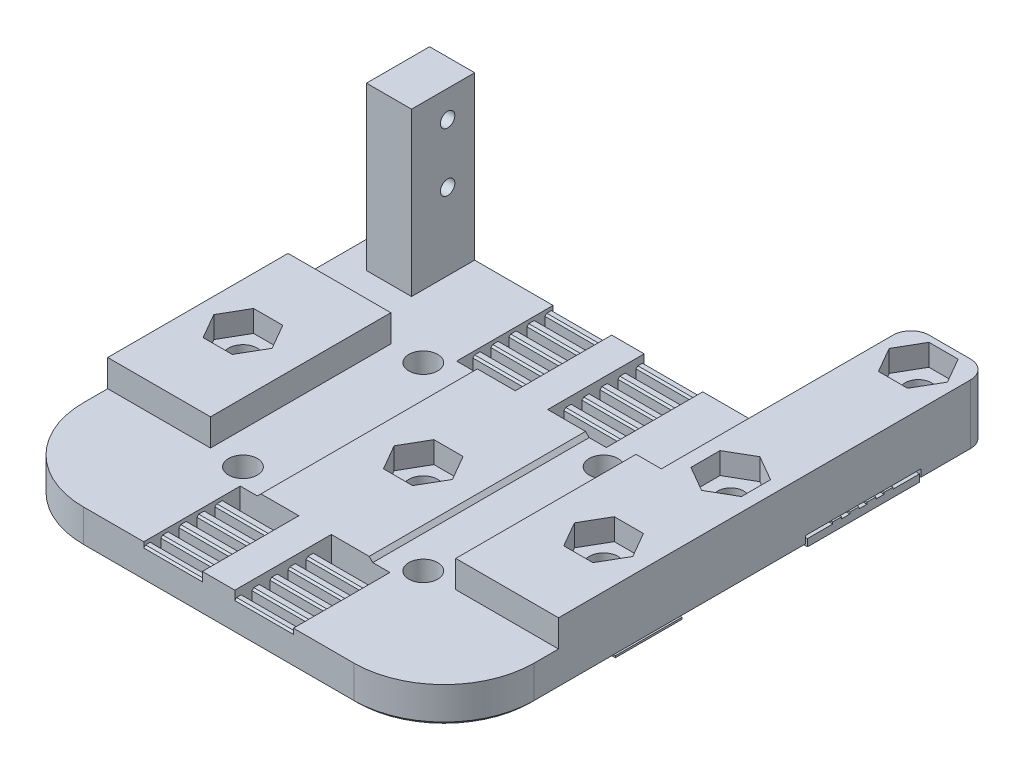
SolidWorks part; units mm, degrees
ref_plane "前视基准面" through (0, 0, 0) normal (0, 0, 1) x (1, 0, 0)
ref_plane "上视基准面" through (0, 0, 0) normal (0, 1, 0) x (1, 0, 0)
ref_plane "右视基准面" through (0, 0, 0) normal (1, 0, 0) x (0, 0, -1)
other "Configuration Table"
sketch "草图1" plane through (0, 0, 0) normal (0, 1, 0) x (1, 0, 0)
  line L1 (0, 0) -> (50, 0)
  line L2 (0, 0) -> (0, 45.4)
  line L3 (0, 45.4) -> (50, 45.4)
  line L4 (50, 0) -> (50, 45.4)
  circle A0 centre (15, 32.7) radius 1.6
  circle A1 centre (35, 32.7) radius 1.6
  circle A2 centre (35, 12.7) radius 1.6
  circle A3 centre (15, 12.7) radius 1.6
  dimension "D3" = 3.2
  dimension "D1" = 50
  dimension "D2" = 45.4
  dimension "D6" = 12.7
  dimension "D7" = 15
  dimension "D5" = 2
extrude "凸台-拉伸1" add sketch "草图1" along normal blind 4
sketch "草图2" plane through (0, 0, 0) normal (0, 0, 1) x (1, 0, 0)
  line L0 (0, 4) -> (50, 4) construction
  line L1 (19, 4) -> (31, 4)
  line L2 (19, 4) -> (19, 4.4)
  line L3 (19, 4.4) -> (31, 4.4)
  line L4 (31, 4) -> (31, 4.4)
  line L5 (0, 0) -> (50, 0) construction
  point P6 (25, 4.4)
  point P9 (25, 0)
  dimension "D1" = 0.4
  dimension "D2" = 12
  dimension "D3" = 0
extrude "凸台-拉伸2" add sketch "草图2" against normal up to surface (45.4 mm away) up to face at (25, 2, -45.4)
chamfer "倒角1" distance 0.4 angle 45 2 edges at (31, 4, -22.7) (19, 4, -22.7)
sketch "草图3" plane through (0, 0, 0) normal (0, -1, 0) x (-1, 0, 0)
  line L0 (0, 45.4) -> (0, 0) construction
  line L1 (0, 18.2) -> (-50, 18.2)
  line L2 (0, 18.2) -> (0, 27.2)
  line L3 (0, 27.2) -> (-50, 27.2)
  line L4 (-50, 18.2) -> (-50, 27.2)
  line L5 (-50, 0) -> (-50, 45.4) construction
  line L6 (0, 0) -> (-50, 0) construction
  point P8 (0, 22.7)
  dimension "D1" = 9
  dimension "D2" = 22.7
extrude "切除-拉伸1" cut sketch "草图3" against normal blind 0.4
sketch "草图4" plane through (0, 0.4, 0) normal (0, -1, 0) x (-1, 0, 0)
  line L0 (0, 18.2) -> (0, 27.2) construction
  circle A0 centre (-5, 22.7) radius 1.6
  circle A1 centre (-25, 22.7) radius 1.6
  circle A2 centre (-45, 22.7) radius 1.6
  point P4 (0, 22.7)
  dimension "D1" = 3.2
  dimension "D4" = 5
extrude "切除-拉伸2" cut sketch "草图4" against normal through all
sketch "草图5" plane through (0, 4, 0) normal (0, 1, 0) x (1, 0, 0)
  line L0 (50, 45.4) -> (31.4, 45.4) construction
  line L1 (50, 45.4) -> (41.4, 45.4)
  line L2 (50, 45.4) -> (50, 60.4)
  line L3 (50, 60.4) -> (41.4, 60.4)
  line L4 (41.4, 45.4) -> (41.4, 60.4)
  line L5 (50, 0) -> (50, 45.4) construction
  dimension "D1" = 8.6
  dimension "D2" = 0
  dimension "D3" = 15
extrude "凸台-拉伸3" add sketch "草图5" against normal blind 4
sketch "草图6" plane through (0, 0, 0) normal (0, -1, 0) x (1, 0, 0)
  line L0 (50, -60.4) -> (41.4, -60.4) construction
  line L1 (50, -27.2) -> (50, -60.4) construction
  circle A0 centre (45.7, -56.9) radius 1.45
  circle A1 centre (45.7, -36.1) radius 1.45
  point P4 (45.7, -60.4)
  dimension "D1" = 2.9
  dimension "D2" = 3.5
  dimension "D3" = 4.3
  dimension "D4" = 0
  dimension "D5" = 20.8
  dimension "D6" = 2.9
extrude "切除-拉伸3" cut sketch "草图6" against normal blind 4
sketch "草图7" plane through (0, 4.4, 0) normal (0, 1, 0) x (1, 0, 0)
  line L1 (28.2332, 22.7) -> (26.6166, 25.5)
  line L2 (26.6166, 25.5) -> (23.3834, 25.5)
  line L3 (23.3834, 25.5) -> (21.7668, 22.7)
  line L4 (21.7668, 22.7) -> (23.3834, 19.9)
  line L5 (23.3834, 19.9) -> (26.6166, 19.9)
  line L6 (26.6166, 19.9) -> (28.2332, 22.7)
  circle A0 centre (25, 22.7) radius 2.8 construction
  dimension "D1" = 5.6
extrude "切除-拉伸4" cut sketch "草图7" against normal blind 2.4
sketch "草图8" plane through (0, 4, 0) normal (0, 1, 0) x (1, 0, 0)
  line L0 (50, 0) -> (50, 60.4) construction
  line L1 (41.4, 32.7) -> (38.6, 32.7)
  line L2 (50, 32.7) -> (50, 12.7)
  line L3 (50, 12.7) -> (38.6, 12.7)
  line L4 (38.6, 32.7) -> (38.6, 12.7)
  line L5 (0, 45.4) -> (0, 0) construction
  line L6 (0, 32.7) -> (11.4, 32.7)
  line L7 (0, 32.7) -> (0, 12.7)
  line L8 (0, 12.7) -> (11.4, 12.7)
  line L9 (11.4, 32.7) -> (11.4, 12.7)
  line L11 (41.4, 60.4) -> (50, 60.4)
  line L12 (41.4, 60.4) -> (41.4, 32.7)
  line L14 (50, 60.4) -> (50, 32.7)
  circle A1 centre (5, 22.7) radius 1.6 construction
  circle A2 centre (45, 22.7) radius 1.6 construction
  circle A3 centre (5, 22.7) radius 1.6
  circle A4 centre (45, 22.7) radius 1.6
  circle A5 centre (45.7, 56.9) radius 1.45
  circle A6 centre (45.7, 36.1) radius 1.45
  point P12 (50, 22.7)
  point P14 (11.4, 22.7)
  dimension "D1" = 27.2
  dimension "D2" = 11.4
  dimension "D3" = 20
  dimension "D4" = 20
extrude "凸台-拉伸4" add sketch "草图8" along normal blind 3
sketch "草图9" plane through (0, 7, 0) normal (0, 1, 0) x (1, 0, 0)
  line L0 (50, 12.7) -> (50, 60.4) construction
  line L1 (8.2332, 22.7) -> (6.6166, 25.5)
  line L2 (6.6166, 25.5) -> (3.3834, 25.5)
  line L3 (3.3834, 25.5) -> (1.7668, 22.7)
  line L4 (1.7668, 22.7) -> (3.3834, 19.9)
  line L5 (3.3834, 19.9) -> (6.6166, 19.9)
  line L6 (6.6166, 19.9) -> (8.2332, 22.7)
  line L7 (48.2332, 22.7) -> (46.6166, 25.5)
  line L8 (46.6166, 25.5) -> (43.3834, 25.5)
  line L9 (43.3834, 25.5) -> (41.7668, 22.7)
  line L10 (41.7668, 22.7) -> (43.3834, 19.9)
  line L11 (43.3834, 19.9) -> (46.6166, 19.9)
  line L12 (46.6166, 19.9) -> (48.2332, 22.7)
  line L13 (44.0834, 54.1) -> (47.3166, 54.1)
  line L14 (47.3166, 54.1) -> (48.9332, 56.9)
  line L15 (48.9332, 56.9) -> (47.3166, 59.7)
  line L16 (47.3166, 59.7) -> (44.0834, 59.7)
  line L17 (44.0834, 59.7) -> (42.4668, 56.9)
  line L18 (42.4668, 56.9) -> (44.0834, 54.1)
  line L19 (48.5, 37.7166) -> (45.7, 39.3332)
  line L20 (45.7, 39.3332) -> (42.9, 37.7166)
  line L21 (42.9, 37.7166) -> (42.9, 34.4834)
  line L22 (42.9, 34.4834) -> (45.7, 32.8668)
  line L23 (45.7, 32.8668) -> (48.5, 34.4834)
  line L24 (48.5, 34.4834) -> (48.5, 37.7166)
  circle A0 centre (5, 22.7) radius 2.8 construction
  circle A1 centre (45, 22.7) radius 2.8 construction
  circle A2 centre (45.7, 56.9) radius 2.8 construction
  circle A3 centre (45.7, 36.1) radius 2.8 construction
  dimension "D1" = 5.6
  dimension "D2" = 5.6
  dimension "D3" = 5.6
  dimension "D4" = 5.6
  dimension "D5" = 0
  dimension "D6" = 90
extrude "切除-拉伸5" cut sketch "草图9" against normal blind 2.4
sketch "草图10" plane through (0, 4, 0) normal (0, 1, 0) x (1, 0, 0)
  line L1 (3, 38.4) -> (8, 38.4)
  line L2 (3, 38.4) -> (3, 45.4)
  line L3 (3, 45.4) -> (8, 45.4)
  line L4 (8, 38.4) -> (8, 45.4)
  line L7 (18.6, 45.4) -> (0, 45.4) construction
  line L8 (0, 45.4) -> (0, 32.7) construction
  dimension "D1" = 7
  dimension "D2" = 5
  dimension "D3" = 3
  dimension "D4" = 0
extrude "凸台-拉伸5" add sketch "草图10" along normal blind 18
sketch "草图11" plane through (3, 0, 0) normal (-1, 0, 0) x (0, 0, 1)
  line L0 (-45.4, 22) -> (-45.4, 4) construction
  line L1 (-45.4, 22) -> (-38.4, 22) construction
  circle A0 centre (-42.4, 19) radius 0.8
  circle A1 centre (-42.4, 12.5) radius 0.8
  dimension "D1" = 6.5
  dimension "D2" = 0
  dimension "D3" = 1.6
  dimension "D4" = 1.6
  dimension "D5" = 3
  dimension "D6" = 3
extrude "切除-拉伸6" cut sketch "草图11" against normal blind 15
sketch "草图12" plane through (0, 4.4, 0) normal (0, 1, 0) x (1, 0, 0)
  line L0 (19, 45.4) -> (31, 45.4) construction
  line L1 (26.8, 45.4) -> (33.3, 45.4)
  line L2 (26.8, 45.4) -> (26.8, 34.7)
  line L3 (26.8, 34.7) -> (33.3, 34.7)
  line L4 (33.3, 45.4) -> (33.3, 34.7)
  line L5 (18.6, 45.4) -> (8, 45.4) construction
  line L6 (16.7, 45.4) -> (23.2, 45.4)
  line L7 (16.7, 45.4) -> (16.7, 34.7)
  line L8 (16.7, 34.7) -> (23.2, 34.7)
  line L9 (23.2, 45.4) -> (23.2, 34.7)
  line L10 (0, 0) -> (18.6, 0) construction
  line L11 (16.7, 0) -> (23.2, 0)
  line L12 (16.7, 0) -> (16.7, 10.7)
  line L13 (16.7, 10.7) -> (23.2, 10.7)
  line L14 (23.2, 0) -> (23.2, 10.7)
  line L16 (26.8, 10.7) -> (33.3, 10.7)
  line L17 (26.8, 10.7) -> (26.8, 0)
  line L18 (26.8, 0) -> (33.3, 0)
  line L19 (33.3, 10.7) -> (33.3, 0)
  circle A0 centre (25, 22.7) radius 1.6 construction
  dimension "D12" = 12
  dimension "D1" = 6.5
  dimension "D2" = 3.6
  dimension "D3" = 6.5
  dimension "D4" = 6.5
  dimension "D5" = 6.5
  dimension "D6" = 3.6
  dimension "D7" = 1.8
  dimension "D8" = 1.8
  dimension "D9" = 12
  dimension "D10" = 12
  dimension "D11" = 12
extrude "切除-拉伸7" cut sketch "草图12" against normal blind 0.8
sketch "草图13" plane through (0, 3.6, 0) normal (0, 1, 0) x (1, 0, 0)
  line L0 (23.2, 34.7) -> (23.2, 45.4) construction
  line L1 (16.7, 34.7) -> (23.2, 34.7)
  line L2 (16.7, 34.7) -> (16.7, 36.5)
  line L3 (16.7, 36.5) -> (23.2, 36.5)
  line L4 (23.2, 34.7) -> (23.2, 36.5)
  line L5 (33.3, 34.7) -> (33.3, 45.4) construction
  line L6 (26.8, 34.7) -> (33.3, 34.7)
  line L7 (26.8, 34.7) -> (26.8, 36.5)
  line L8 (26.8, 36.5) -> (33.3, 36.5)
  line L9 (33.3, 34.7) -> (33.3, 36.5)
  line L10 (23.2, 0) -> (23.2, 10.7) construction
  line L11 (16.7, 10.7) -> (23.2, 10.7)
  line L12 (16.7, 10.7) -> (16.7, 8.9)
  line L13 (16.7, 8.9) -> (23.2, 8.9)
  line L14 (23.2, 10.7) -> (23.2, 8.9)
  line L15 (33.3, 0) -> (33.3, 10.7) construction
  line L16 (26.8, 10.7) -> (33.3, 10.7)
  line L17 (26.8, 10.7) -> (26.8, 8.9)
  line L18 (26.8, 8.9) -> (33.3, 8.9)
  line L19 (33.3, 10.7) -> (33.3, 8.9)
  dimension "D1" = 1.8
  dimension "D2" = 1.8
  dimension "D3" = 1.8
  dimension "D4" = 1.8
extrude "切除-拉伸8" cut sketch "草图13" against normal through all
sketch "草图14" plane through (0, 3.6, 0) normal (0, 1, 0) x (1, 0, 0)
  line L0 (16.7, 34.7) -> (16.7, 45.4) construction
  line L1 (16.7, 37.5) -> (23.2, 37.5)
  line L2 (16.7, 37.5) -> (16.7, 38.5)
  line L3 (16.7, 38.5) -> (23.2, 38.5)
  line L4 (23.2, 37.5) -> (23.2, 38.5)
  line L5 (23.2, 36.5) -> (23.2, 45.4) construction
  line L6 (23.2, 36.5) -> (16.7, 36.5) construction
  line L7 (16.7, 39.5) -> (16.7, 40.5)
  line L8 (16.7, 39.5) -> (23.2, 39.5)
  line L9 (23.2, 39.5) -> (23.2, 40.5)
  line L10 (16.7, 40.5) -> (23.2, 40.5)
  line L11 (16.7, 41.5) -> (16.7, 42.5)
  line L12 (16.7, 41.5) -> (23.2, 41.5)
  line L13 (23.2, 41.5) -> (23.2, 42.5)
  line L14 (16.7, 42.5) -> (23.2, 42.5)
  line L15 (16.7, 43.5) -> (16.7, 44.5)
  line L16 (16.7, 43.5) -> (23.2, 43.5)
  line L17 (23.2, 43.5) -> (23.2, 44.5)
  line L18 (16.7, 44.5) -> (23.2, 44.5)
  line L19 (33.3, 36.5) -> (33.3, 45.4) construction
  line L20 (33.3, 37.5) -> (26.8, 37.5)
  line L21 (33.3, 37.5) -> (33.3, 38.5)
  line L22 (33.3, 38.5) -> (26.8, 38.5)
  line L23 (26.8, 37.5) -> (26.8, 38.5)
  line L24 (26.8, 45.4) -> (26.8, 36.5) construction
  line L25 (33.3, 39.5) -> (33.3, 40.5)
  line L26 (33.3, 39.5) -> (26.8, 39.5)
  line L27 (26.8, 39.5) -> (26.8, 40.5)
  line L28 (33.3, 40.5) -> (26.8, 40.5)
  line L29 (33.3, 41.5) -> (33.3, 42.5)
  line L30 (33.3, 41.5) -> (26.8, 41.5)
  line L31 (26.8, 41.5) -> (26.8, 42.5)
  line L32 (33.3, 42.5) -> (26.8, 42.5)
  line L33 (33.3, 43.5) -> (33.3, 44.5)
  line L34 (33.3, 43.5) -> (26.8, 43.5)
  line L35 (26.8, 43.5) -> (26.8, 44.5)
  line L36 (33.3, 44.5) -> (26.8, 44.5)
  line L37 (33.3, 10.7) -> (33.3, 0) construction
  line L38 (33.3, 7.9) -> (26.8, 7.9)
  line L39 (33.3, 7.9) -> (33.3, 6.9)
  line L40 (33.3, 6.9) -> (26.8, 6.9)
  line L41 (26.8, 7.9) -> (26.8, 6.9)
  line L42 (23.2, 0) -> (23.2, 8.9) construction
  line L43 (23.2, 7.9) -> (16.7, 7.9)
  line L44 (23.2, 7.9) -> (23.2, 6.9)
  line L45 (23.2, 6.9) -> (16.7, 6.9)
  line L46 (16.7, 7.9) -> (16.7, 6.9)
  line L47 (16.7, 8.9) -> (16.7, 0) construction
  line L48 (26.8, 8.9) -> (33.3, 8.9) construction
  line L49 (16.7, 8.9) -> (23.2, 8.9) construction
  line L50 (33.3, 5.9) -> (33.3, 4.9)
  line L51 (33.3, 5.9) -> (26.8, 5.9)
  line L52 (26.8, 5.9) -> (26.8, 4.9)
  line L53 (33.3, 4.9) -> (26.8, 4.9)
  line L54 (23.2, 5.9) -> (23.2, 4.9)
  line L55 (23.2, 5.9) -> (16.7, 5.9)
  line L56 (16.7, 5.9) -> (16.7, 4.9)
  line L57 (23.2, 4.9) -> (16.7, 4.9)
  line L58 (33.3, 3.9) -> (33.3, 2.9)
  line L59 (33.3, 3.9) -> (26.8, 3.9)
  line L60 (26.8, 3.9) -> (26.8, 2.9)
  line L61 (33.3, 2.9) -> (26.8, 2.9)
  line L62 (23.2, 3.9) -> (23.2, 2.9)
  line L63 (23.2, 3.9) -> (16.7, 3.9)
  line L64 (16.7, 3.9) -> (16.7, 2.9)
  line L65 (23.2, 2.9) -> (16.7, 2.9)
  line L66 (33.3, 1.9) -> (33.3, 0.9)
  line L67 (33.3, 1.9) -> (26.8, 1.9)
  line L68 (26.8, 1.9) -> (26.8, 0.9)
  line L69 (33.3, 0.9) -> (26.8, 0.9)
  line L70 (23.2, 1.9) -> (23.2, 0.9)
  line L71 (23.2, 1.9) -> (16.7, 1.9)
  line L72 (16.7, 1.9) -> (16.7, 0.9)
  line L73 (23.2, 0.9) -> (16.7, 0.9)
  dimension "D1" = 1
  dimension "D2" = 1
  dimension "D5" = 1
  dimension "D6" = 1
  dimension "D7" = 1
  dimension "D8" = 1
  dimension "D3" = 4
  dimension "D4" = 4
  dimension "D9" = 4
extrude "切除-拉伸9" cut sketch "草图14" against normal blind 1.2
fillet "圆角1" radius 10 2 edges at (50, 2, 0) (0, 2, 0)
fillet "圆角2" radius 2 3 edges at (41.4, 3.5, -60.4) (50, 3.5, -60.4) (0, 2, -45.4)
sketch "草图15" plane through (0, 0, 0) normal (0, -1, 0) x (1, 0, 0)
  line L0 (50, -18.2) -> (0, -18.2) construction
  line L1 (0, -19) -> (50, -19)
  line L2 (0, -19) -> (0, -26.4)
  line L3 (0, -26.4) -> (50, -26.4)
  line L4 (50, -19) -> (50, -26.4)
  line L5 (0, -27.2) -> (50, -27.2) construction
  line L6 (0, -18.2) -> (0, -27.2) construction
  line L7 (50, -27.2) -> (50, -18.2) construction
  dimension "D1" = 0.8
  dimension "D2" = 0.8
  dimension "D3" = 0
  dimension "D4" = 0
extrude "凸台-拉伸6" add sketch "草图15" against normal blind 0.2 separate body
sketch "草图16" plane through (0, 0, 0) normal (0, -1, 0) x (-1, 0, 0)
  line L14 (-48.421, 52.9) -> (-42.4, 52.9)
  line L16 (-48.5, 49.901) -> (-42.4, 49.901)
  line L17 (-42.4, 52.9) -> (-42.4, 49.901)
  line L18 (-48.5, 43.099) -> (-42.4, 43.099)
  line L20 (-48.421, 40.1) -> (-42.4, 40.1)
  line L21 (-42.4, 43.099) -> (-42.4, 40.1)
  line L22 (-41.4, 58.4) -> (-41.4, 45.4) construction
  line L24 (-48.421, 52.9) -> (-50, 52.9)
  line L25 (-48.5, 49.901) -> (-48.5, 43.099)
  line L26 (-48.421, 40.1) -> (-50, 40.1)
  line L27 (-50, 52.9) -> (-50, 40.1)
  circle A2 centre (-45.7, 36.1) radius 1.45 construction
  circle A3 centre (-45.7, 56.9) radius 1.45 construction
  dimension "D6" = 4
  dimension "D1" = 1.5
  dimension "D3" = 1
  dimension "D4" = 1
  dimension "D5" = 4
  dimension "D7" = 3
  dimension "D8" = 3
extrude "切除-拉伸10" cut sketch "草图16" against normal blind 1.2
chamfer "倒角2" distance 0.2 angle 45 40 edges at (30.05, 3.6, -7.9) (30.05, 3.6, -8.9) (30.05, 3.6, -5.9) (30.05, 3.6, -6.9) (30.05, 3.6, -3.9) (30.05, 3.6, -4.9) (30.05, 3.6, -1.9) (30.05, 3.6, -2.9) (30.05, 3.6, 0) (30.05, 3.6, -0.9) (19.95, 3.6, 0) (19.95, 3.6, -0.9) (19.95, 3.6, -1.9) (19.95, 3.6, -2.9) (19.95, 3.6, -3.9) (19.95, 3.6, -4.9) (19.95, 3.6, -5.9) (19.95, 3.6, -6.9) (19.95, 3.6, -7.9) (19.95, 3.6, -8.9) (30.05, 3.6, -41.5) (30.05, 3.6, -45.4) (30.05, 3.6, -44.5) (30.05, 3.6, -43.5) (30.05, 3.6, -42.5) (30.05, 3.6, -40.5) (30.05, 3.6, -39.5) (30.05, 3.6, -38.5) (30.05, 3.6, -37.5) (30.05, 3.6, -36.5) (19.95, 3.6, -36.5) (19.95, 3.6, -37.5) (19.95, 3.6, -38.5) (19.95, 3.6, -39.5) (19.95, 3.6, -40.5) (19.95, 3.6, -41.5) (19.95, 3.6, -42.5) (19.95, 3.6, -43.5) (19.95, 3.6, -44.5) (19.95, 3.6, -45.4)
chamfer "倒角3" distance 0.4 angle 45 45 edges at (35, 0, -31.1) (15, 0, -31.1) (25, 0, -27.2) (50, 0, -55.65) (50, 0, -33.65) (49.4142, 0, -59.8142) (45.7, 0, -60.4) (41.9858, 0, -59.8142) (41.4, 0, -51.9) (21.7, 0, -45.4) (0.5858, 0, -44.8142) (0, 0, -35.3) (45.7, 0, -37.55) (45.7, 0, -58.35) (19.95, 0, -36.5) (23.2, 0, -35.6) (19.95, 0, -34.7) (16.7, 0, -35.6) (30.05, 0, -36.5) (33.3, 0, -35.6) (30.05, 0, -34.7) (26.8, 0, -35.6) (35, 0, -11.1) (15, 0, -11.1) (25, 0, -18.2) (0, 0, -14.1) (2.9289, 0, -2.9289) (25, 0, 0) (47.0711, 0, -2.9289) (50, 0, -14.1) (30.05, 0, -10.7) (33.3, 0, -9.8) (30.05, 0, -8.9) (26.8, 0, -9.8) (19.95, 0, -10.7) (23.2, 0, -9.8) (19.95, 0, -8.9) (16.7, 0, -9.8) (46.2, 0, -40.1) (42.4, 0, -41.5995) (45.45, 0, -43.099) (48.5, 0, -46.5) (45.45, 0, -49.901) (42.4, 0, -51.4005) (46.2, 0, -52.9)
sketch "草图17" plane through (0, 0, 0) normal (0, -1, 0) x (-1, 0, 0)
  line L0 (-50, 52.9) -> (-50, 40.1) construction
  line L1 (-42.5484, 40.3138) -> (-50, 40.3138)
  line L2 (-42.5484, 40.3138) -> (-42.5484, 42.8662)
  line L3 (-42.5484, 42.8662) -> (-48.6931, 42.8662)
  line L4 (-50, 40.3138) -> (-50, 42.8662)
  line L7 (-50, 42.8662) -> (-50, 50.0981)
  line L9 (-48.6931, 42.8662) -> (-48.6931, 50.0981)
  line L10 (-48.6931, 50.0981) -> (-42.5484, 50.0981)
  line L11 (-50, 50.0981) -> (-50, 52.7447)
  line L12 (-50, 52.7447) -> (-42.5484, 52.7447)
  line L13 (-42.5484, 50.0981) -> (-42.5484, 52.7447)
extrude "凸台-拉伸7" add sketch "草图17" against normal blind 0.8 separate body
sketch "草图18" plane through (0, 0.8, 0) normal (0, 1, 0) x (1, 0, 0)
  line L0 (48.6931, 50.0981) -> (42.5484, 50.0981) construction
  line L1 (42.5484, 52.7447) -> (43.5484, 52.7447)
  line L2 (42.5484, 52.7447) -> (42.5484, 50.0981)
  line L3 (42.5484, 50.0981) -> (43.5484, 50.0981)
  line L4 (43.5484, 52.7447) -> (43.5484, 50.0981)
  line L5 (42.5484, 42.8662) -> (48.6931, 42.8662) construction
  line L6 (42.5484, 40.3138) -> (43.5484, 40.3138)
  line L7 (42.5484, 40.3138) -> (42.5484, 42.8662)
  line L8 (42.5484, 42.8662) -> (43.5484, 42.8662)
  line L9 (43.5484, 40.3138) -> (43.5484, 42.8662)
  line L10 (44.5484, 52.7447) -> (44.5484, 50.0981)
  line L11 (44.5484, 52.7447) -> (45.5484, 52.7447)
  line L12 (45.5484, 52.7447) -> (45.5484, 50.0981)
  line L13 (44.5484, 50.0981) -> (45.5484, 50.0981)
  line L14 (44.5484, 40.3138) -> (44.5484, 42.8662)
  line L15 (44.5484, 40.3138) -> (45.5484, 40.3138)
  line L16 (45.5484, 40.3138) -> (45.5484, 42.8662)
  line L17 (44.5484, 42.8662) -> (45.5484, 42.8662)
  line L18 (46.5484, 52.7447) -> (46.5484, 50.0981)
  line L19 (46.5484, 52.7447) -> (47.5484, 52.7447)
  line L20 (47.5484, 52.7447) -> (47.5484, 50.0981)
  line L21 (46.5484, 50.0981) -> (47.5484, 50.0981)
  line L22 (46.5484, 40.3138) -> (46.5484, 42.8662)
  line L23 (46.5484, 40.3138) -> (47.5484, 40.3138)
  line L24 (47.5484, 40.3138) -> (47.5484, 42.8662)
  line L25 (46.5484, 42.8662) -> (47.5484, 42.8662)
  line L26 (48.5484, 52.7447) -> (48.5484, 50.0981)
  line L27 (48.5484, 52.7447) -> (49.5484, 52.7447)
  line L28 (49.5484, 52.7447) -> (49.5484, 50.0981)
  line L29 (48.5484, 50.0981) -> (49.5484, 50.0981)
  line L30 (48.5484, 40.3138) -> (48.5484, 42.8662)
  line L31 (48.5484, 40.3138) -> (49.5484, 40.3138)
  line L32 (49.5484, 40.3138) -> (49.5484, 42.8662)
  line L33 (48.5484, 42.8662) -> (49.5484, 42.8662)
  line L34 (48.6931, 42.8662) -> (48.6931, 50.0981) construction
  line L35 (48.6931, 43.1066) -> (50, 43.1066)
  line L36 (48.6931, 43.1066) -> (48.6931, 44.1066)
  line L37 (48.6931, 44.1066) -> (50, 44.1066)
  line L38 (50, 43.1066) -> (50, 44.1066)
  line L39 (50, 52.7447) -> (50, 40.3138) construction
  line L40 (48.6931, 45.0066) -> (48.6931, 46.0066)
  line L41 (48.6931, 45.0066) -> (50, 45.0066)
  line L42 (50, 45.0066) -> (50, 46.0066)
  line L43 (48.6931, 46.0066) -> (50, 46.0066)
  line L44 (48.6931, 46.9066) -> (48.6931, 47.9066)
  line L45 (48.6931, 46.9066) -> (50, 46.9066)
  line L46 (50, 46.9066) -> (50, 47.9066)
  line L47 (48.6931, 47.9066) -> (50, 47.9066)
  line L48 (48.6931, 48.8066) -> (48.6931, 49.8066)
  line L49 (48.6931, 48.8066) -> (50, 48.8066)
  line L50 (50, 48.8066) -> (50, 49.8066)
  line L51 (48.6931, 49.8066) -> (50, 49.8066)
  dimension "D1" = 1
  dimension "D3" = 1
  dimension "D2" = 4
  dimension "D4" = 4
extrude "凸台-拉伸8" add sketch "草图18" along normal blind 0.2 contours L50 L9 L44 L51 | L4 L48 L47 L46 | L12 L48 L10 L46 | L20 L48 L18 L46 | L50 L16 L44 L14 | L50 L24 L44 L22 | L33 L44 L30 L50 L32 | L48 L51 L28 L26 L46 | L47 L45 L49 | L43 L45 L41 L49 | L37 L45 L35 L49 | L10 L13 L12 L11 | L18 L21 L20 L19 | L48 L51 L50 L49 region at (43.0484, 0.8, -51.4214) region at (43.0484, 0.8, -41.59) region at (45.0484, 0.8, -51.4214) region at (45.0484, 0.8, -41.59) region at (47.0484, 0.8, -51.4214) region at (47.0484, 0.8, -41.59) region at (49.0484, 0.8, -51.4214) region at (49.0484, 0.8, -41.59) region at (49.3465, 0.8, -43.6066) region at (49.3465, 0.8, -45.5066) region at (49.3465, 0.8, -47.4066)
equation "\"D7@草图1\"=\"D1@草图1\"/2-10"
equation "\"D6@草图1\"=\"D2@草图1\"/2-10"
equation "\"D2@草图3\"=\"D2@草图1\"/2"
equation "\"D4@草图4\"=\"D1@草图1\"/2-20"
equation "\"D2@草图8\"=\"D1@草图1\"/2-\"D1@草图8\"/2"
